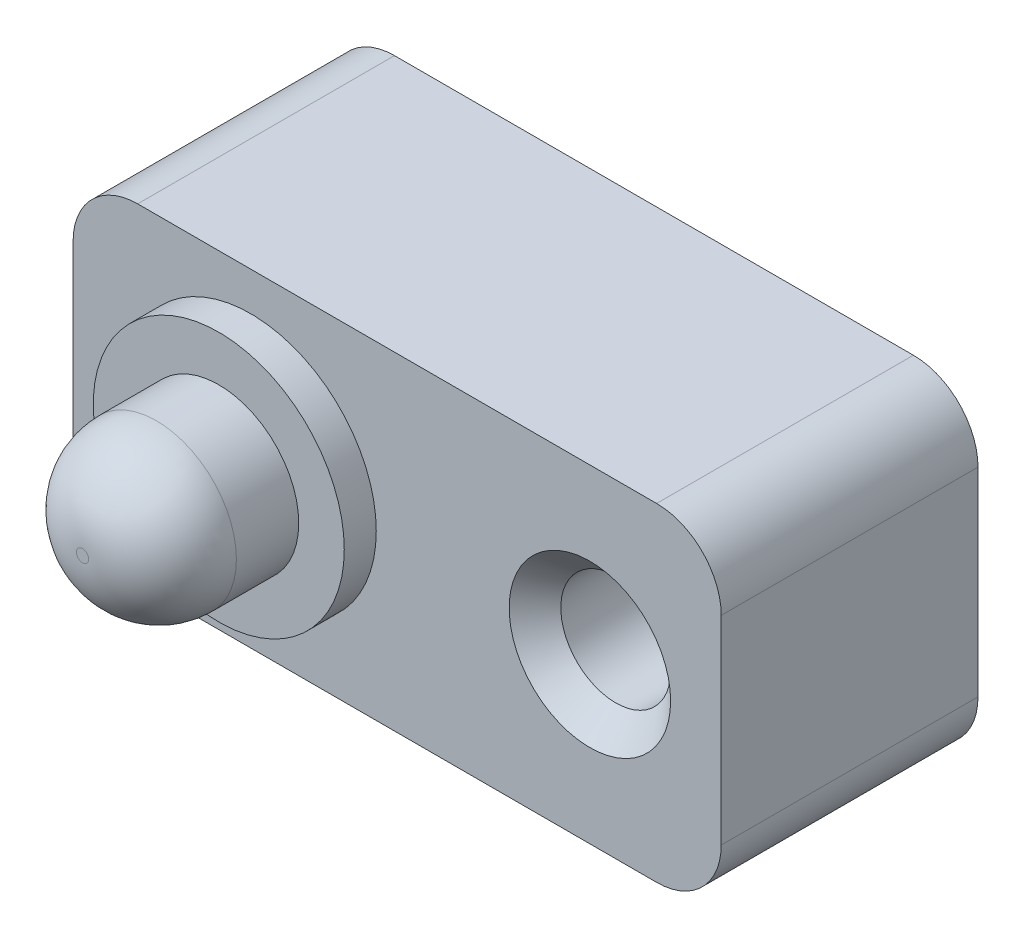
SolidWorks part; units mm, degrees
ref_plane "Front" through (0, 0, 0) normal (0, 0, 1) x (1, 0, 0)
ref_plane "Top" through (0, 0, 0) normal (0, 1, 0) x (1, 0, 0)
ref_plane "Right" through (0, 0, 0) normal (1, 0, 0) x (0, 0, -1)
sketch "Sketch1" plane through (0, 0, 0) normal (0, 0, 1) x (1, 0, 0)
  line L1 (0, 0) -> (20.066, 0)
  line L2 (0, 0) -> (0, 10.16)
  line L3 (0, 10.16) -> (20.066, 10.16)
  line L4 (20.066, 0) -> (20.066, 10.16)
  dimension "D1" = 20.066
  dimension "D2" = 10.16
extrude "Boss-Extrude1" add sketch "Sketch1" along normal blind 7.9502
sketch "Sketch2" plane through (0, 0, 7.9502) normal (0, 0, 1) x (1, 0, 0)
  line L0 (0, 10.16) -> (0, 0) construction
  line L1 (5.5, 10.16) -> (5.5, 0) construction
  line L2 (20.066, 10.16) -> (0, 10.16) construction
  line L3 (0, 0) -> (20.066, 0) construction
  circle A0 centre (5.5, 5.08) radius 3.8862
  dimension "D1" = 7.7724
  dimension "D2" = 5.5
extrude "Boss-Extrude2" add sketch "Sketch2" along normal blind 0.9906
sketch "Sketch3" plane through (0, 0, 8.9408) normal (0, 0, 1) x (1, 0, 0)
  circle A0 centre (5.5, 5.08) radius 2.4765
  dimension "D1" = 4.953
extrude "Boss-Extrude3" add sketch "Sketch3" along normal blind 4.2164
hole_wizard "CSK for M3 SFHCS1" positions "Sketch4" profile "Sketch5" countersink size "M3" standard "ANSI Metric" end condition through all
sketch "Sketch4" plane through (0, 0, 7.9502) normal (0, 0, 1) x (1, 0, 0)
  line L0 (16, 10.16) -> (16, 0) construction
  line L1 (20.066, 10.16) -> (0, 10.16) construction
  line L2 (0, 0) -> (20.066, 0) construction
  circle A0 centre (5.5, 5.08) radius 2.4765 construction
  point P0 (16, 5.08)
  point P13 (0, 0)
  point P14 (0, 0)
  dimension "D1" = 10.5
sketch "Sketch5" plane through (16, 5.08, 7.9502) normal (1, 0, 0) x (0, -1, 0)
  line L0 (0, 0) -> (0, 7.9502)
  line L1 (0, 7.9502) -> (1.7, 7.9502)
  line L2 (1.7, 7.9502) -> (1.7, 0.8)
  line L3 (1.7, 0.8) -> (2.5, 0)
  line L5 (2.5, 0) -> (0, 0)
  line L6 (-1.7, 0.8) -> (-2.5, 0) construction
  line L11 (0, -6.35) -> (0, 107.95) construction
  dimension "Thru Hole Dia." = 3.4
  dimension "Thru Hole Depth" = 7.9502
  dimension "Near C'Sink Dia." = 5
  dimension "Near C'Sink Angle" = 90
fillet "Fillet1" radius 2.286 1 edges at (7.9765, 5.08, 13.1572)
fillet "Fillet2" radius 2 4 edges at (0, 0, 3.9751) (0, 10.16, 3.9751) (20.066, 0, 3.9751) (20.066, 10.16, 3.9751)
